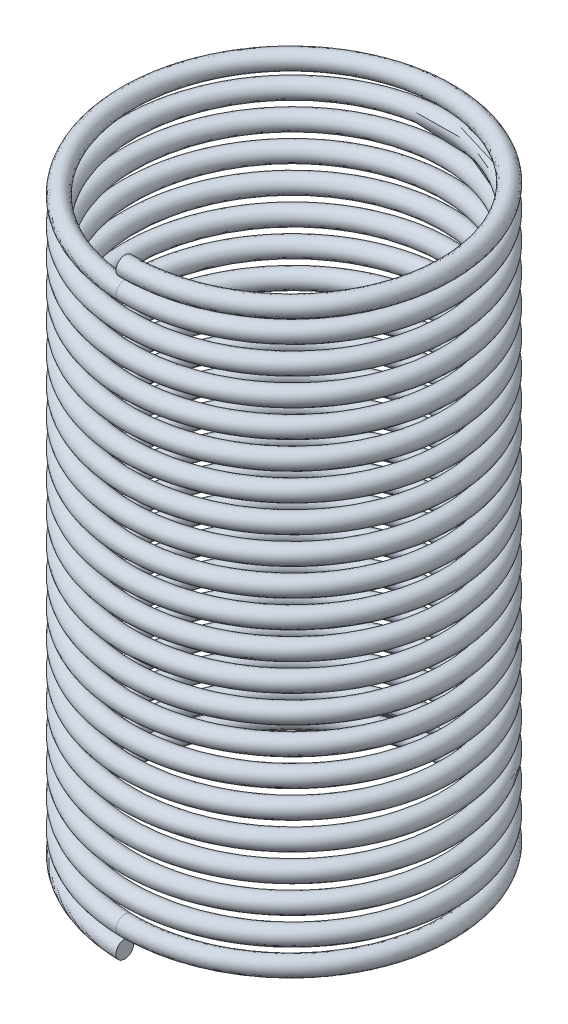
SolidWorks part; units mm, degrees
note: '?' marks a value the reader was unsure of.
ref_plane "Front Plane" through (0, 0, 0) normal (0, 0, 1) x (1, 0, 0)
ref_plane "Top Plane" through (0, 0, 0) normal (0, 1, 0) x (1, 0, 0)
ref_plane "Right Plane" through (0, 0, 0) normal (1, 0, 0) x (0, 0, -1)
sketch "Sketch3" plane through (0, 0, 0) normal (0, 1, 0) x (1, 0, 0)
  line L0 (0, 0) -> (-35.9738, 35.9738) construction
  circle A0 centre (0, 0) radius 4.5
  dimension "D1" = 9
curve "Helix/Spiral1" pitch 0.7725 height 15.45 turns 20
sketch "Sketch5" plane through (0, 0, 0) normal (0, 1, 0) x (1, 0, 0)
  circle A0 centre (0, 0) radius 4.5
  dimension "D1" = 9
curve "Helix/Spiral2" pitch 0.6 height 0.6 turns 1
ref_plane "Plane2" through (0, 15.45, 0) normal (0, 1, 0) x (1, 0, 0)
sketch "Sketch7" plane through (0, 15.45, 0) normal (0, 1, 0) x (1, 0, 0)
  circle A0 centre (0, 0) radius 4.5
  dimension "D1" = 9
curve "Helix/Spiral3" pitch 0.6 height 0.6 turns 1
ref_plane "Plane3" through (0, 16.05, 4.5) normal (-0.9998, 0.0212, 0) x (0, 0, 1)
ref_plane "Plane4" through (0, -0.6, 4.5) normal (0.9998, -0.0212, 0) x (0, 0, -1)
sketch "Sketch9" plane through (0, -0.6, 4.5) normal (0.9998, -0.0212, 0) x (0, 0, -1)
  line L0 (0.2732, -0.2147) -> (-0.2268, -0.2147) construction
  circle A0 centre (0.0232, 0.0353) radius 0.25
  dimension "D1" = 0.5
curve "CompCurve1"
sweep "Sweep3" add profiles "Sketch9" path "CompCurve1"
sketch "TopCenterline" plane through (-0.3404, 0.0072, 0) normal (-0.9998, 0.0212, 0) x (0, 0, 1)
  line L0 (4.7268, 16.3317) -> (4.2268, 16.3317) construction
sketch "Sketch12" plane through (0, 0, 0) normal (1, 0, 0) x (0, 0, -1)
  line L0 (0, 0) -> (0, 43.2413) construction
ref_axis "Axis1" through (0, 0, 0) along (0, 1, 0)?
ref_plane "BottomPlane" through (0, -0.8146, 0) normal (0, 1, 0) x (1, 0, 0)
ref_plane "TopPlane" through (0, 16.3352, 0) normal (0, 1, 0) x (1, 0, 0)
